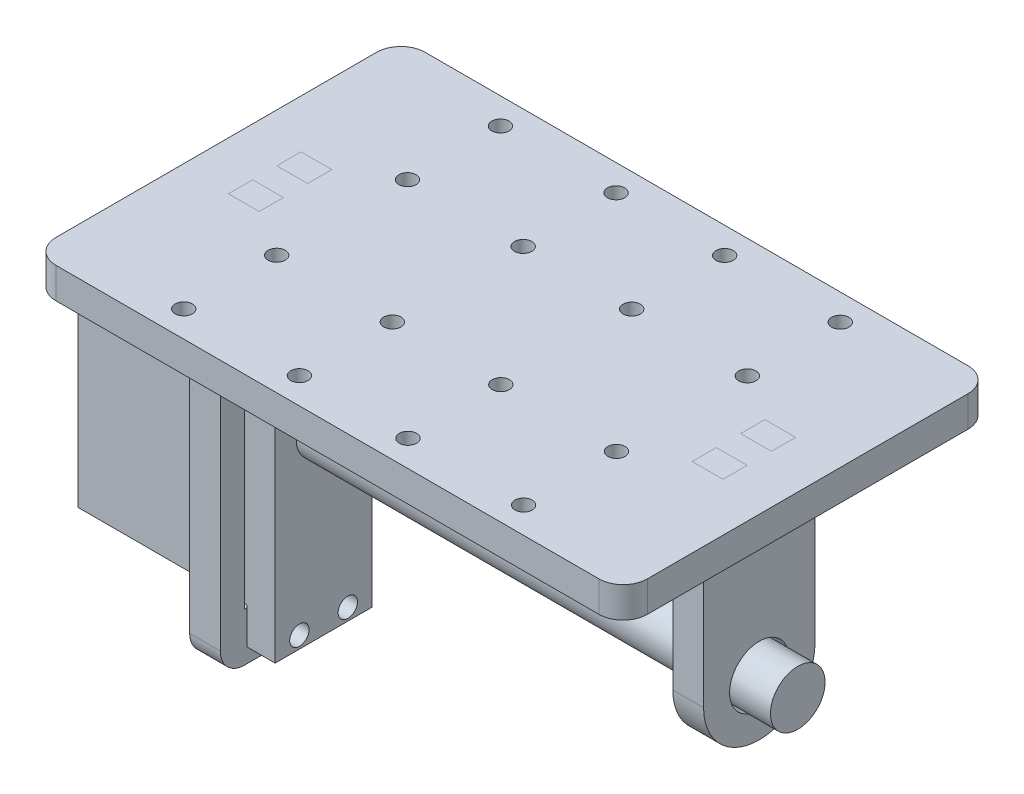
SolidWorks part; units mm, degrees
ref_plane "Front Plane" through (0, 0, 0) normal (0, 0, 1) x (1, 0, 0)
ref_plane "Top Plane" through (0, 0, 0) normal (0, 1, 0) x (1, 0, 0)
ref_plane "Right Plane" through (0, 0, 0) normal (1, 0, 0) x (0, 0, -1)
sketch "Sketch1" plane through (0, 0, 0) normal (1, 0, 0) x (0, 0, -1)
  line L0 (20, 40) -> (20, 47.5)
  line L1 (0, 0) -> (20, 0)
  line L2 (0, 0) -> (0, 40)
  line L3 (0, 40) -> (20, 40)
  line L4 (20, 0) -> (20, 40)
  line L5 (20, 47.5) -> (0, 47.5)
  line L6 (0, 47.5) -> (0, 40)
  line L7 (0, 0) -> (0, -7.5)
  line L8 (0, -7.5) -> (20, -7.5)
  line L9 (20, -7.5) -> (20, 0)
  line L10 (10, 47.5) -> (10, -7.5) construction
  circle A0 centre (10, 30.25) radius 5.64
  circle A1 centre (5, 45) radius 2
  circle A2 centre (5, -5) radius 2
  circle A3 centre (15, 45) radius 2
  circle A4 centre (15, -5) radius 2
  dimension "D1" = 11.28
  dimension "D10" = 4
  dimension "D11" = 4
  dimension "D8" = 5
  dimension "D2" = 40
  dimension "D3" = 20
  dimension "D4" = 9.75
  dimension "D5" = 10
  dimension "D6" = 7.5
  dimension "D7" = 7.5
  dimension "D9" = 5
  dimension "D12" = 5
extrude "Boss-Extrude2" add sketch "Sketch1" against normal blind 37 and the other way blind 3.7 contours L1 L4 L3 L2 A0 | L4 A0 L2 L1 | A0 region at (0, 18.5368, -10)
extrude "Boss-Extrude3" add sketch "Sketch1<3>" along normal blind 101.6 contours A0 | A0 region at (0, 30.25, -10)
sketch "Sketch1<3>" plane through (0, 0, 0) normal (1, 0, 0) x (0, 0, -1) same geometry as "Sketch1"
ref_plane "Plane2" through (87.3, 0, 0) normal (1, 0, 0) x (0, 0, -1)
ref_plane "Plane3" through (-2.1, 0, 0) normal (1, 0, 0) x (0, 0, -1)
sketch "Sketch2" plane through (87.3, 0, 0) normal (1, 0, 0) x (0, 0, -1)
  line L1 (0, 40) -> (20, 40) construction
  line L2 (21.5, 30.25) -> (21.5, 40)
  line L3 (-1.5, 30.25) -> (-1.5, 40)
  line L4 (-1.5, 40) -> (-1.5, 62.75)
  line L6 (21.5, 62.75) -> (21.5, 40)
  line L8 (17.5, 69.1) -> (12.5, 69.1)
  line L9 (12.5, 69.1) -> (12.5, 62.75)
  line L15 (7.5, 62.75) -> (7.5, 69.1)
  line L16 (7.5, 69.1) -> (2.5, 69.1)
  line L19 (12.5, 62.75) -> (7.5, 62.75)
  line L20 (17.5, 69.1) -> (17.5, 62.75)
  line L21 (17.5, 62.75) -> (21.5, 62.75)
  line L22 (2.5, 69.1) -> (2.5, 62.75)
  line L23 (2.5, 62.75) -> (-1.5, 62.75)
  circle A1 centre (10, 30.25) radius 5.64 construction
  arc A2 (-1.5, 30.25) -> (21.5, 30.25) centre (10, 30.25) ccw
  circle A3 centre (10, 30.25) radius 6.14
  dimension "D1" = 32.5
  dimension "D6" = 0.5
  dimension "D2" = 6.35
  dimension "D3" = 23
  dimension "D4" = 5
  dimension "D5" = 5
  dimension "D7" = 5
  dimension "D8" = 4
extrude "Boss-Extrude4" add sketch "Sketch2" along normal blind 6.35 separate body contours L3 A2 L2 L6 L4 region at (87.3, 45.132, -10)
sketch "Sketch3" plane through (-2.1, 0, 0) normal (1, 0, 0) x (0, 0, -1)
  line L0 (20.5, 40.5) -> (-0.5, 40.5)
  line L1 (-0.5, 40.5) -> (-0.5, -0.5)
  line L2 (-0.5, -0.5) -> (20.5, -0.5)
  line L3 (20.5, -0.5) -> (20.5, 40.5)
  line L9 (-5.5, 62.75) -> (-5.5, -5.5)
  line L10 (-0.5, -10.5) -> (20.5, -10.5)
  line L11 (25.5, -5.5) -> (25.5, 62.75)
  line L13 (10, 47.5) -> (10, -7.5) construction
  line L14 (-0.5, 20) -> (-5.5, 20) construction
  line L15 (20.5, 20) -> (25.5, 20) construction
  line L27 (20, 0) -> (20, 40) construction
  line L28 (0, 40) -> (20, 40) construction
  line L29 (0, 0) -> (20, 0) construction
  line L30 (0, 0) -> (0, 40) construction
  line L31 (25.5, 62.75) -> (17.5, 62.75)
  line L32 (17.5, 62.75) -> (17.5, 69.1)
  line L33 (17.5, 69.1) -> (12.5, 69.1)
  line L34 (17.5, 69.1) -> (12.5, 69.1) construction
  line L35 (12.5, 69.1) -> (12.5, 62.75)
  line L36 (12.5, 62.75) -> (7.5, 62.75)
  line L37 (7.5, 62.75) -> (7.5, 69.1)
  line L38 (7.5, 69.1) -> (2.5, 69.1)
  line L39 (2.5, 69.1) -> (2.5, 62.75)
  line L40 (2.5, 62.75) -> (-5.5, 62.75)
  arc A0 (-0.5, -10.5) -> (-5.5, -5.5) centre (-0.5, -5.5) cw
  arc A1 (25.5, -5.5) -> (20.5, -10.5) centre (20.5, -5.5) cw
  circle A4 centre (5, -5) radius 2
  circle A5 centre (5, 45) radius 2
  circle A6 centre (5, 45) radius 2 construction
  circle A7 centre (5, -5) radius 2 construction
  circle A8 centre (15, 45) radius 2
  circle A9 centre (15, -5) radius 2
  dimension "D8" = 5
  dimension "D9" = 5
  dimension "D4" = 0.5
  dimension "D5" = 0.5
  dimension "D1" = 5
  dimension "D2" = 10
  dimension "D3" = 5
  dimension "D6" = 0.5
  dimension "D7" = 0.5
extrude "Boss-Extrude5" add sketch "Sketch3" against normal blind 6.35
extrude "Boss-Extrude8" add sketch "Sketch1<4>" against normal blind 2.1 and the other way blind 3.7 contours L5 L6 L3 L0 | L8 L9 L1 L7 | L1 L10 L8 L9 A4 | L5 L10 L3 L0 A3 region at (0, 40.125, -15) region at (0, 40.125, -5) region at (0, -3.75, -19.875) region at (0, -3.75, -9.875)
sketch "Sketch1<4>" plane through (0, 0, 0) normal (1, 0, 0) x (0, 0, -1) same geometry as "Sketch1"
sketch "Sketch7" plane through (0, 62.75, 0) normal (0, 1, 0) x (1, 0, 0)
  line L0 (-13.45, 48.1) -> (98.65, 48.1)
  line L5 (103.65, 43.1) -> (103.65, -23.1)
  line L6 (98.65, -28.1) -> (-13.45, -28.1)
  line L7 (-18.45, -23.1) -> (-18.45, 43.1)
  line L12 (93.65, 17.5) -> (93.65, 12.5) construction
  line L23 (93.65, 12.5) -> (87.3, 12.5)
  line L28 (87.3, 7.5) -> (93.65, 7.5)
  line L32 (-8.45, 12.5) -> (-8.45, 7.5) construction
  line L33 (93.65, 12.5) -> (93.65, 17.5)
  line L34 (93.65, 17.5) -> (87.3, 17.5)
  line L35 (87.3, 17.5) -> (87.3, 12.5)
  line L38 (87.3, 2.5) -> (87.3, 7.5)
  line L39 (-8.45, 17.5) -> (-2.1, 17.5)
  line L40 (-2.1, 17.5) -> (-2.1, 12.5)
  line L41 (-2.1, 12.5) -> (-8.45, 12.5)
  line L42 (-8.45, 12.5) -> (-8.45, 17.5)
  line L43 (-2.1, 7.5) -> (-2.1, 2.5)
  line L44 (-2.1, 2.5) -> (-8.45, 2.5)
  line L45 (-8.45, 2.5) -> (-8.45, 7.5)
  line L46 (-8.45, 7.5) -> (-2.1, 7.5)
  line L47 (7.522, -22.691) -> (31.398, -22.691) construction
  line L48 (42.6, 33.1) -> (42.6, -13.1) construction
  line L49 (65.74, -13.1) -> (19.46, -13.1) construction
  line L50 (7.522, -3.509) -> (31.398, -3.509) construction
  line L51 (77.678, -22.691) -> (53.802, -22.691) construction
  line L52 (19.46, -3.509) -> (19.46, -22.691) construction
  line L53 (65.74, -3.509) -> (65.74, -22.691) construction
  line L54 (93.65, 7.5) -> (93.65, 2.5)
  line L55 (93.65, 2.5) -> (87.3, 2.5)
  line L56 (77.678, -3.509) -> (53.802, -3.509) construction
  line L57 (24.538, 10) -> (60.662, 10) construction
  line L58 (7.522, 42.691) -> (31.398, 42.691) construction
  line L59 (7.522, 23.509) -> (31.398, 23.509) construction
  line L60 (19.46, 23.509) -> (19.46, 42.691) construction
  line L61 (77.678, 42.691) -> (53.802, 42.691) construction
  line L62 (77.678, 23.509) -> (53.802, 23.509) construction
  line L63 (65.74, 23.509) -> (65.74, 42.691) construction
  line L64 (65.74, 33.1) -> (19.46, 33.1) construction
  arc A0 (98.65, 48.1) -> (103.65, 43.1) centre (98.65, 43.1) cw
  arc A2 (-13.45, 48.1) -> (-18.45, 43.1) centre (-13.45, 43.1) ccw
  arc A3 (-18.45, -23.1) -> (-13.45, -28.1) centre (-13.45, -23.1) ccw
  arc A4 (98.65, -28.1) -> (103.65, -23.1) centre (98.65, -23.1) ccw
  circle A5 centre (31.398, -22.691) radius 1.778
  circle A6 centre (7.522, -22.691) radius 1.778
  circle A7 centre (7.522, -3.509) radius 1.778
  circle A8 centre (31.398, -3.509) radius 1.778
  circle A9 centre (77.678, -22.691) radius 1.778
  circle A10 centre (53.802, -22.691) radius 1.778
  circle A11 centre (53.802, -3.509) radius 1.778
  circle A12 centre (77.678, -3.509) radius 1.778
  circle A13 centre (31.398, 42.691) radius 1.778
  circle A14 centre (7.522, 42.691) radius 1.778
  circle A15 centre (7.522, 23.509) radius 1.778
  circle A16 centre (31.398, 23.509) radius 1.778
  circle A17 centre (77.678, 42.691) radius 1.778
  circle A18 centre (53.802, 42.691) radius 1.778
  circle A19 centre (53.802, 23.509) radius 1.778
  circle A20 centre (77.678, 23.509) radius 1.778
  point P24 (19.46, -22.691)
  point P31 (19.46, -3.509)
  point P33 (19.46, -13.1)
  point P39 (42.6, 10)
  point P78 (42.6, 10)
  line M63 (-2.1, 7.5) -> (-2.1, 12.5)
  line M64 (-2.1, 12.5) -> (-8.45, 12.5)
  line M65 (-8.45, 12.5) -> (-8.45, 7.5)
  line M66 (-8.45, 7.5) -> (-2.1, 7.5)
  dimension "D5" = 5
  dimension "D6" = 5
  dimension "D13" = 3.556
  dimension "D14" = 3.556
  dimension "D15" = 3.556
  dimension "D16" = 3.556
  dimension "D1" = 44.7
  dimension "D2" = 46.2
  dimension "D3" = 10
  dimension "D4" = 10
  dimension "D7" = 15
  dimension "D8" = 23.14
  dimension "D9" = 19.182
  dimension "D10" = 23.876
  dimension "D11" = 2.5
  dimension "D12" = 15
extrude "Boss-Extrude11" add sketch "Sketch7" along normal blind 6.35 separate body contours L7 L6 L5 L0 L23 L28 | M66 M63 M64 M65 region at (42.7696, 62.75, -10) region at (-5.275, 62.75, -10)
